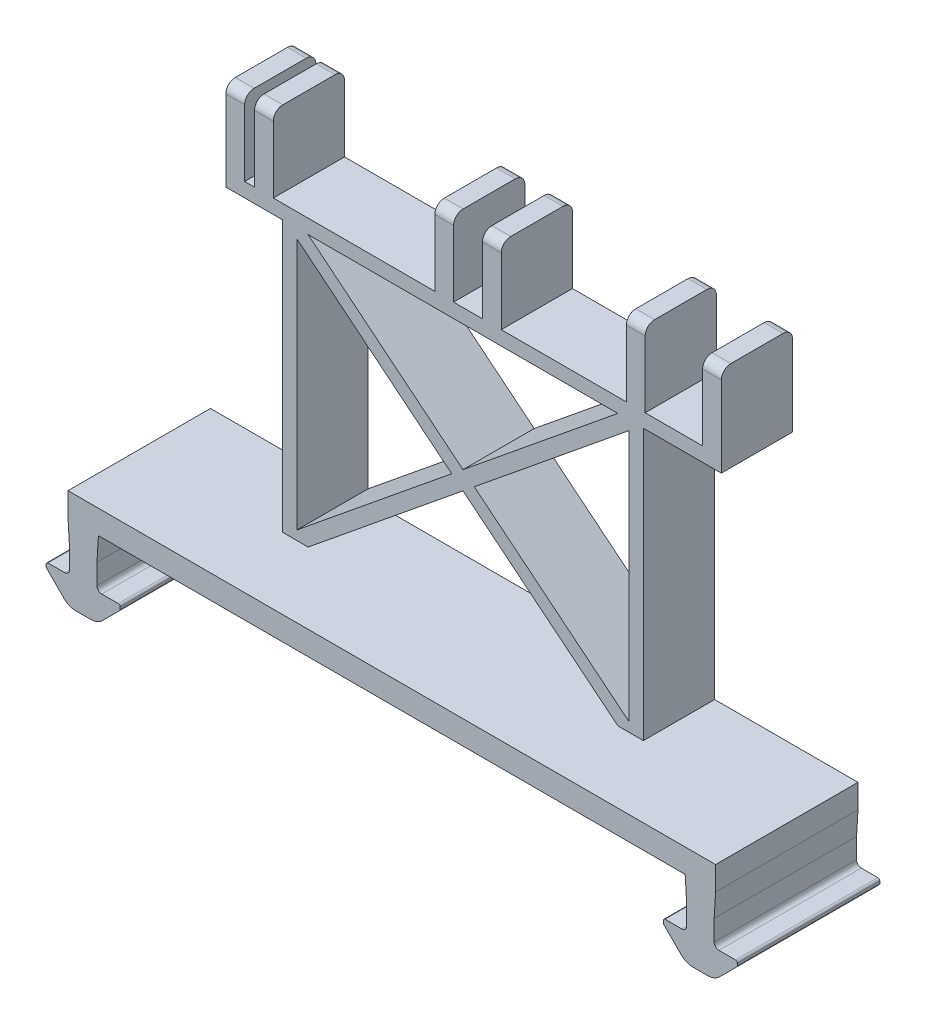
SolidWorks part; units mm, degrees
ref_plane "Front Plane" through (0, 0, 0) normal (0, 0, 1) x (1, 0, 0)
ref_plane "Top Plane" through (0, 0, 0) normal (0, 1, 0) x (1, 0, 0)
ref_plane "Right Plane" through (0, 0, 0) normal (1, 0, 0) x (0, 0, -1)
sketch "Sketch1" plane through (0, 0, 0) normal (0, 0, 1) x (1, 0, 0)
  line L7 (0, 0) -> (0, 26.663) construction
  line L8 (-2.0169, 6.858) -> (2.0169, 6.858)
  line L9 (5.3755, 8.2492) -> (10.0266, 12.9003)
  line L10 (10.287, 13.5289) -> (10.287, 14.0979)
  line L11 (9.398, 14.9869) -> (4.953, 14.9869)
  line L12 (4.064, 15.8759) -> (4.064, 27.6869)
  line L13 (0, 0) -> (20.2214, 20.2214) construction
  line L14 (-4.064, 15.8759) -> (-4.064, 27.6869)
  line L15 (-9.398, 14.9869) -> (-4.953, 14.9869)
  line L16 (-10.287, 13.5289) -> (-10.287, 14.0979)
  line L17 (-5.3755, 8.2492) -> (-10.0266, 12.9003)
  line L19 (163.0831, 6.858) -> (167.1169, 6.858)
  line L20 (170.4755, 8.2492) -> (175.1266, 12.9003)
  line L21 (175.387, 13.5289) -> (175.387, 14.0979)
  line L22 (174.498, 14.9869) -> (170.053, 14.9869)
  line L23 (169.164, 15.8759) -> (169.164, 27.6869)
  line L24 (161.036, 15.8759) -> (161.036, 27.6869)
  line L25 (155.702, 14.9869) -> (160.147, 14.9869)
  line L26 (154.813, 13.5289) -> (154.813, 14.0979)
  line L27 (159.7245, 8.2492) -> (155.0734, 12.9003)
  line L29 (-4.064, 27.6869) -> (-4.064, 34.0369)
  line L30 (-4.064, 34.0369) -> (169.164, 34.0369)
  line L31 (169.164, 34.0369) -> (169.164, 27.6869)
  line L32 (4.064, 27.6869) -> (161.036, 27.6869)
  arc A0 (10.0266, 12.9003) -> (10.287, 13.5289) centre (9.398, 13.5289) ccw
  arc A1 (9.398, 14.9869) -> (10.287, 14.0979) centre (9.398, 14.0979) cw
  arc A2 (4.953, 14.9869) -> (4.064, 15.8759) centre (4.953, 15.8759) cw
  arc A3 (2.0169, 6.858) -> (5.3755, 8.2492) centre (2.0169, 11.6078) ccw
  arc A4 (-2.0169, 6.858) -> (-5.3755, 8.2492) centre (-2.0169, 11.6078) cw
  arc A5 (-4.953, 14.9869) -> (-4.064, 15.8759) centre (-4.953, 15.8759) ccw
  arc A6 (-9.398, 14.9869) -> (-10.287, 14.0979) centre (-9.398, 14.0979) ccw
  arc A7 (-10.0266, 12.9003) -> (-10.287, 13.5289) centre (-9.398, 13.5289) cw
  arc A8 (175.1266, 12.9003) -> (175.387, 13.5289) centre (174.498, 13.5289) ccw
  arc A9 (174.498, 14.9869) -> (175.387, 14.0979) centre (174.498, 14.0979) cw
  arc A10 (170.053, 14.9869) -> (169.164, 15.8759) centre (170.053, 15.8759) cw
  arc A11 (167.1169, 6.858) -> (170.4755, 8.2492) centre (167.1169, 11.6078) ccw
  arc A12 (163.0831, 6.858) -> (159.7245, 8.2492) centre (163.0831, 11.6078) cw
  arc A13 (160.147, 14.9869) -> (161.036, 15.8759) centre (160.147, 15.8759) ccw
  arc A14 (155.702, 14.9869) -> (154.813, 14.0979) centre (155.702, 14.0979) ccw
  arc A15 (155.0734, 12.9003) -> (154.813, 13.5289) centre (155.702, 13.5289) cw
  point P1 (-4.064, 14.9869)
  point P20 (4.064, 14.9869)
  point P34 (0, 6.858)
  point P36 (161.036, 14.9869)
  point P63 (165.1, 6.858)
  dimension "D6" = 0.889
  dimension "D9" = 4.7498
  dimension "D1" = 12.7
  dimension "D2" = 4.064
  dimension "D3" = 6.858
  dimension "D4" = 10.287
  dimension "D5" = 2.032
  dimension "D7" = 0.569
  dimension "D8" = 45
  dimension "D11" = 165.1
  dimension "D12" = 6.35
  dimension "D10" = 2
extrude "Boss-Extrude2" add sketch "Sketch1" along normal blind 38.1
sketch "Sketch7" plane through (0, 0, 0) normal (0, 0, 1) x (1, 0, 0)
  line L0 (82.55, 68.2701) -> (82.55, 42.7511) construction
  line L1 (130.81, 106.4269) -> (169.164, 106.4269)
  line L3 (169.164, 34.0369) -> (-4.064, 34.0369) construction
  line L4 (-4.064, 34.0369) -> (-4.064, 15.8759) construction
  line L6 (34.29, 106.4269) -> (34.29, 34.0369)
  line L7 (34.29, 34.0369) -> (38.1, 34.0369)
  line L8 (130.81, 106.4269) -> (130.81, 34.0369)
  line L9 (-4.064, 110.2369) -> (169.164, 110.2369)
  line L10 (-4.064, 110.2369) -> (-4.064, 106.4269)
  line L11 (-4.064, 106.4269) -> (34.29, 106.4269)
  line L12 (169.164, 110.2369) -> (169.164, 106.4269)
  line L13 (38.1, 34.0369) -> (38.1, 106.4269)
  line L14 (127, 106.4269) -> (127, 34.0369)
  line L15 (38.1, 106.4269) -> (127, 106.4269)
  line L16 (127, 34.0369) -> (130.81, 34.0369)
  point P4 (82.55, 34.0369)
  point P15 (82.55, 110.2369)
  dimension "D1" = 72.39
  dimension "D2" = 3.81
  dimension "D3" = 3.81
  dimension "D4" = 44.45
extrude "Boss-Extrude6" add sketch "Sketch7" along normal blind 19.05
sketch "Sketch6" plane through (0, 110.2369, 0) normal (0, 1, 0) x (1, 0, 0)
  line L1 (19.1008, 0) -> (24.1808, 0)
  line L2 (19.1008, 0) -> (19.1008, -19.05)
  line L3 (19.1008, -19.05) -> (24.1808, -19.05)
  line L4 (24.1808, 0) -> (24.1808, -19.05)
  line L24 (169.164, 0) -> (130.81, 0) construction
  line L25 (26.7208, 0) -> (26.7208, -19.05)
  line L26 (-4.064, -38.1) -> (-4.064, 0) construction
  line L27 (26.7208, -19.05) -> (31.8008, -19.05)
  line L28 (31.8008, 0) -> (31.8008, -19.05)
  line L29 (26.7208, 0) -> (31.8008, 0)
  line L30 (75.0062, 0) -> (75.0062, -19.05)
  line L31 (75.0062, -19.05) -> (80.0862, -19.05)
  line L32 (80.0862, 0) -> (80.0862, -19.05)
  line L33 (75.0062, 0) -> (80.0862, 0)
  line L34 (87.7062, 0) -> (87.7062, -19.05)
  line L35 (87.7062, -19.05) -> (92.7862, -19.05)
  line L36 (92.7862, 0) -> (92.7862, -19.05)
  line L37 (87.7062, 0) -> (92.7862, 0)
  line L38 (126.2634, 0) -> (126.2634, -19.05)
  line L39 (126.2634, -19.05) -> (131.3434, -19.05)
  line L40 (131.3434, 0) -> (131.3434, -19.05)
  line L41 (126.2634, 0) -> (131.3434, 0)
  line L42 (146.5834, 0) -> (146.5834, -19.05)
  line L43 (146.5834, -19.05) -> (151.6634, -19.05)
  line L44 (151.6634, 0) -> (151.6634, -19.05)
  line L45 (146.5834, 0) -> (151.6634, 0)
  line L46 (-4.064, -38.1) -> (-4.064, 0) construction
  dimension "D1" = 5.08
  dimension "D2" = 19.05
  dimension "D4" = 28.2448
  dimension "D5" = 5.08
  dimension "D6" = 5.08
  dimension "D3" = 5.08
  dimension "D7" = 5.08
  dimension "D8" = 5.08
  dimension "D9" = 30.7848
  dimension "D10" = 84.1502
  dimension "D11" = 91.7702
  dimension "D12" = 150.6474
  dimension "D13" = 135.4074
extrude "Boss-Extrude5" add sketch "Sketch6" along normal blind 20.32
sketch "Sketch10" plane through (0, 0, 0) normal (0, 0, 1) x (1, 0, 0)
  line L1 (19.1008, 110.2369) -> (-4.064, 110.2369)
  line L2 (19.1008, 110.2369) -> (19.1008, 106.4269)
  line L3 (19.1008, 106.4269) -> (-4.064, 106.4269)
  line L4 (-4.064, 110.2369) -> (-4.064, 106.4269)
  line L5 (151.6634, 110.2369) -> (169.164, 110.2369)
  line L6 (151.6634, 110.2369) -> (151.6634, 106.4269)
  line L7 (151.6634, 106.4269) -> (169.164, 106.4269)
  line L8 (169.164, 110.2369) -> (169.164, 106.4269)
extrude "Cut-Extrude3" cut sketch "Sketch10" along normal up to surface (19.05 mm away) up to face at (82.6968, 107.9085, 19.05)
fillet "Fillet1" radius 2.54 12 edges at (149.1234, 130.5569, 0) (128.8034, 130.5569, 0) (149.1234, 130.5569, 19.05) (128.8034, 130.5569, 19.05) (90.2462, 130.5569, 0) (90.2462, 130.5569, 19.05) (77.5462, 130.5569, 19.05) (77.5462, 130.5569, 0) (29.2608, 130.5569, 0) (21.6408, 130.5569, 0) (21.6408, 130.5569, 19.05) (29.2608, 130.5569, 19.05)
sketch "Sketch11" plane through (0, 0, 0) normal (0, 0, 1) x (1, 0, 0)
  line L0 (38.1, 103.9702) -> (79.533, 70.2319)
  line L1 (38.1, 34.0369) -> (38.1, 106.4269) construction
  line L2 (169.164, 34.0369) -> (-4.064, 34.0369) construction
  line L3 (123.983, 34.0369) -> (127, 34.0369)
  line L4 (127, 34.0369) -> (127, 36.4936)
  line L5 (127, 106.4269) -> (127, 34.0369) construction
  line L6 (127, 36.4936) -> (85.567, 70.2319)
  line L7 (38.1, 106.4269) -> (127, 106.4269) construction
  line L8 (41.117, 106.4269) -> (38.1, 106.4269)
  line L9 (38.1, 106.4269) -> (38.1, 103.9702)
  line L10 (123.983, 106.4269) -> (127, 106.4269)
  line L11 (127, 106.4269) -> (127, 103.9702)
  line L12 (127, 103.9702) -> (85.567, 70.2319)
  line L13 (41.117, 34.0369) -> (38.1, 34.0369)
  line L14 (38.1, 34.0369) -> (38.1, 36.4936)
  line L15 (38.1, 36.4936) -> (79.533, 70.2319)
  line L16 (38.1, 34.0369) -> (127, 106.4269) construction
  line L17 (38.1, 106.4269) -> (127, 34.0369) construction
  line L18 (82.55, 67.7752) -> (41.117, 34.0369)
  line L19 (82.55, 67.7752) -> (123.983, 34.0369)
  line L20 (82.55, 72.6886) -> (123.983, 106.4269)
  line L21 (82.55, 72.6886) -> (41.117, 106.4269)
  dimension "D1" = 3.81
  dimension "D2" = 3.81
extrude "Boss-Extrude7" add sketch "Sketch11" along normal up to surface (19.05 mm away) up to face at (82.7151, 106.665, 19.05)
sketch "Sketch3" plane through (0, 0, 38.1) normal (0, 0, 1) x (1, 0, 0)
  line L27 (-3.937, 21.3369) -> (3.937, 21.3369) construction
  line L28 (4.064, 27.6869) -> (3.683, 21.3369)
  line L29 (-4.064, 27.6869) -> (-3.683, 21.3369)
  line L40 (-4.064, 34.0369) -> (-4.064, 15.8759) construction
  line L41 (-1004.064, 27.6869) -> (4.064, 27.6869) construction
  line L42 (161.036, 27.6869) -> (161.417, 21.3369)
  line L43 (169.164, 27.6869) -> (168.783, 21.3369)
  line L44 (169.164, 15.8759) -> (169.164, 34.0369) construction
  line L57 (5.1061, 8.5186) -> (9.7572, 13.1697)
  line L58 (9.906, 13.5289) -> (9.906, 14.0979)
  line L59 (9.398, 14.6059) -> (4.953, 14.6059)
  line L61 (3.683, 15.8759) -> (3.683, 28.0679)
  line L62 (3.683, 28.0679) -> (161.417, 28.0679)
  line L66 (161.417, 28.0679) -> (161.417, 15.8759)
  line L67 (160.147, 14.6059) -> (155.702, 14.6059)
  line L68 (155.194, 14.0979) -> (155.194, 13.5289)
  line L69 (155.3428, 13.1697) -> (159.9939, 8.5186)
  line L80 (163.0831, 7.239) -> (167.1169, 7.239)
  line L81 (170.2061, 8.5186) -> (174.8572, 13.1697)
  line L82 (175.006, 13.5289) -> (175.006, 14.0979)
  line L85 (174.498, 14.6059) -> (170.053, 14.6059)
  line L86 (168.783, 15.8759) -> (168.783, 33.6559)
  line L91 (168.783, 33.6559) -> (-3.683, 33.6559)
  line L93 (-3.683, 33.6559) -> (-3.683, 15.8759)
  line L95 (-4.953, 14.6059) -> (-9.398, 14.6059)
  line L97 (-9.906, 14.0979) -> (-9.906, 13.5289)
  line L99 (-9.7572, 13.1697) -> (-5.1061, 8.5186)
  line L101 (-2.0169, 7.239) -> (2.0169, 7.239)
  line L103 (5.1061, 8.5186) -> (9.7572, 13.1697)
  line L105 (9.906, 13.5289) -> (9.906, 14.0979)
  line L109 (9.398, 14.6059) -> (4.953, 14.6059)
  line L110 (3.683, 15.8759) -> (3.683, 21.3369)
  line L112 (161.417, 21.3369) -> (161.417, 15.8759)
  line L113 (160.147, 14.6059) -> (155.702, 14.6059)
  line L114 (155.194, 14.0979) -> (155.194, 13.5289)
  line L115 (155.3428, 13.1697) -> (159.9939, 8.5186)
  line L116 (163.0831, 7.239) -> (167.1169, 7.239)
  line L117 (170.2061, 8.5186) -> (174.8572, 13.1697)
  line L118 (175.006, 13.5289) -> (175.006, 14.0979)
  line L119 (174.498, 14.6059) -> (170.053, 14.6059)
  line L120 (168.783, 15.8759) -> (168.783, 21.3369)
  line L122 (-3.683, 21.3369) -> (-3.683, 15.8759)
  line L123 (-4.953, 14.6059) -> (-9.398, 14.6059)
  line L124 (-9.906, 14.0979) -> (-9.906, 13.5289)
  line L125 (-9.7572, 13.1697) -> (-5.1061, 8.5186)
  line L126 (-2.0169, 7.239) -> (2.0169, 7.239)
  line L137 (161.036, 27.6869) -> (1318.008, 27.6869) construction
  line L138 (19.1008, 130.5569) -> (24.1808, 130.5569) construction
  line L139 (24.13, 130.5569) -> (26.7716, 130.5569)
  line L140 (24.13, 130.5569) -> (24.13, 110.2369)
  line L141 (24.13, 110.2369) -> (26.7716, 110.2369)
  line L142 (26.7716, 130.5569) -> (26.7716, 110.2369)
  line L143 (126.2634, 130.5569) -> (131.3434, 130.5569) construction
  line L144 (80.0354, 130.5569) -> (87.757, 130.5569)
  line L145 (80.0354, 130.5569) -> (80.0354, 110.2369)
  line L146 (80.0354, 110.2369) -> (87.757, 110.2369)
  line L147 (87.757, 130.5569) -> (87.757, 110.2369)
  line L148 (131.2926, 130.5569) -> (146.6342, 130.5569)
  line L149 (131.2926, 130.5569) -> (131.2926, 110.2369)
  line L150 (131.2926, 110.2369) -> (146.6342, 110.2369)
  line L151 (146.6342, 130.5569) -> (146.6342, 110.2369)
  line L152 (126.2634, 110.2369) -> (92.7862, 110.2369) construction
  line L153 (24.1808, 128.0169) -> (24.1808, 110.2369) construction
  line L154 (26.7208, 128.0169) -> (26.7208, 110.2369) construction
  line L155 (80.0862, 128.0169) -> (80.0862, 110.2369) construction
  line L156 (87.7062, 128.0169) -> (87.7062, 110.2369) construction
  line L157 (5.3755, 8.2492) -> (10.0266, 12.9003)
  line L158 (10.287, 13.5289) -> (10.287, 14.0979)
  line L159 (9.398, 14.9869) -> (4.953, 14.9869)
  line L160 (4.064, 15.8759) -> (4.064, 27.6869)
  line L161 (4.064, 27.6869) -> (161.036, 27.6869)
  line L162 (161.036, 27.6869) -> (161.036, 15.8759)
  line L163 (160.147, 14.9869) -> (155.702, 14.9869)
  line L164 (154.813, 14.0979) -> (154.813, 13.5289)
  line L165 (155.0734, 12.9003) -> (159.7245, 8.2492)
  line L166 (163.0831, 6.858) -> (167.1169, 6.858)
  line L167 (170.4755, 8.2492) -> (175.1266, 12.9003)
  line L168 (175.387, 13.5289) -> (175.387, 14.0979)
  line L169 (174.498, 14.9869) -> (170.053, 14.9869)
  line L170 (169.164, 15.8759) -> (169.164, 34.0369)
  line L171 (169.164, 34.0369) -> (-4.064, 34.0369)
  line L172 (-4.064, 34.0369) -> (-4.064, 15.8759)
  line L173 (-4.953, 14.9869) -> (-9.398, 14.9869)
  line L174 (-10.287, 14.0979) -> (-10.287, 13.5289)
  line L175 (-10.0266, 12.9003) -> (-5.3755, 8.2492)
  line L176 (-2.0169, 6.858) -> (2.0169, 6.858)
  line L177 (5.3755, 8.2492) -> (10.0266, 12.9003)
  line L178 (10.287, 13.5289) -> (10.287, 14.0979)
  line L179 (9.398, 14.9869) -> (4.953, 14.9869)
  line L180 (4.064, 15.8759) -> (4.064, 27.6869)
  line L182 (161.036, 27.6869) -> (161.036, 15.8759)
  line L183 (160.147, 14.9869) -> (155.702, 14.9869)
  line L184 (154.813, 14.0979) -> (154.813, 13.5289)
  line L185 (155.0734, 12.9003) -> (159.7245, 8.2492)
  line L186 (163.0831, 6.858) -> (167.1169, 6.858)
  line L187 (170.4755, 8.2492) -> (175.1266, 12.9003)
  line L188 (175.387, 13.5289) -> (175.387, 14.0979)
  line L189 (174.498, 14.9869) -> (170.053, 14.9869)
  line L190 (169.164, 15.8759) -> (169.164, 27.6869)
  line L192 (-4.064, 27.6869) -> (-4.064, 15.8759)
  line L193 (-4.953, 14.9869) -> (-9.398, 14.9869)
  line L194 (-10.287, 14.0979) -> (-10.287, 13.5289)
  line L195 (-10.0266, 12.9003) -> (-5.3755, 8.2492)
  line L196 (-2.0169, 6.858) -> (2.0169, 6.858)
  line L197 (87.7062, 130.5569) -> (92.7862, 130.5569) construction
  line L198 (131.3434, 128.0169) -> (131.3434, 110.2369) construction
  line L199 (146.5834, 128.0169) -> (146.5834, 110.2369) construction
  arc A96 (2.0169, 7.239) -> (5.1061, 8.5186) centre (2.0169, 11.6078) ccw
  arc A97 (9.7572, 13.1697) -> (9.906, 13.5289) centre (9.398, 13.5289) ccw
  arc A98 (9.906, 14.0979) -> (9.398, 14.6059) centre (9.398, 14.0979) ccw
  arc A99 (3.683, 15.8759) -> (4.953, 14.6059) centre (4.953, 15.8759) ccw
  arc A100 (160.147, 14.6059) -> (161.417, 15.8759) centre (160.147, 15.8759) ccw
  arc A101 (155.702, 14.6059) -> (155.194, 14.0979) centre (155.702, 14.0979) ccw
  arc A102 (155.194, 13.5289) -> (155.3428, 13.1697) centre (155.702, 13.5289) ccw
  arc A103 (159.9939, 8.5186) -> (163.0831, 7.239) centre (163.0831, 11.6078) ccw
  arc A104 (167.1169, 7.239) -> (170.2061, 8.5186) centre (167.1169, 11.6078) ccw
  arc A105 (174.8572, 13.1697) -> (175.006, 13.5289) centre (174.498, 13.5289) ccw
  arc A106 (175.006, 14.0979) -> (174.498, 14.6059) centre (174.498, 14.0979) ccw
  arc A107 (168.783, 15.8759) -> (170.053, 14.6059) centre (170.053, 15.8759) ccw
  arc A108 (-4.953, 14.6059) -> (-3.683, 15.8759) centre (-4.953, 15.8759) ccw
  arc A109 (-9.398, 14.6059) -> (-9.906, 14.0979) centre (-9.398, 14.0979) ccw
  arc A110 (-9.906, 13.5289) -> (-9.7572, 13.1697) centre (-9.398, 13.5289) ccw
  arc A111 (-5.1061, 8.5186) -> (-2.0169, 7.239) centre (-2.0169, 11.6078) ccw
  arc A112 (2.0169, 7.239) -> (5.1061, 8.5186) centre (2.0169, 11.6078) ccw
  arc A113 (9.7572, 13.1697) -> (9.906, 13.5289) centre (9.398, 13.5289) ccw
  arc A114 (9.906, 14.0979) -> (9.398, 14.6059) centre (9.398, 14.0979) ccw
  arc A115 (3.683, 15.8759) -> (4.953, 14.6059) centre (4.953, 15.8759) ccw
  arc A116 (160.147, 14.6059) -> (161.417, 15.8759) centre (160.147, 15.8759) ccw
  arc A117 (155.702, 14.6059) -> (155.194, 14.0979) centre (155.702, 14.0979) ccw
  arc A118 (155.194, 13.5289) -> (155.3428, 13.1697) centre (155.702, 13.5289) ccw
  arc A119 (159.9939, 8.5186) -> (163.0831, 7.239) centre (163.0831, 11.6078) ccw
  arc A120 (167.1169, 7.239) -> (170.2061, 8.5186) centre (167.1169, 11.6078) ccw
  arc A121 (174.8572, 13.1697) -> (175.006, 13.5289) centre (174.498, 13.5289) ccw
  arc A122 (175.006, 14.0979) -> (174.498, 14.6059) centre (174.498, 14.0979) ccw
  arc A123 (168.783, 15.8759) -> (170.053, 14.6059) centre (170.053, 15.8759) ccw
  arc A124 (-4.953, 14.6059) -> (-3.683, 15.8759) centre (-4.953, 15.8759) ccw
  arc A125 (-9.398, 14.6059) -> (-9.906, 14.0979) centre (-9.398, 14.0979) ccw
  arc A126 (-9.906, 13.5289) -> (-9.7572, 13.1697) centre (-9.398, 13.5289) ccw
  arc A127 (-5.1061, 8.5186) -> (-2.0169, 7.239) centre (-2.0169, 11.6078) ccw
  arc A144 (2.0169, 6.858) -> (5.3755, 8.2492) centre (2.0169, 11.6078) ccw
  arc A145 (10.0266, 12.9003) -> (10.287, 13.5289) centre (9.398, 13.5289) ccw
  arc A146 (10.287, 14.0979) -> (9.398, 14.9869) centre (9.398, 14.0979) ccw
  arc A147 (4.064, 15.8759) -> (4.953, 14.9869) centre (4.953, 15.8759) ccw
  arc A148 (160.147, 14.9869) -> (161.036, 15.8759) centre (160.147, 15.8759) ccw
  arc A149 (155.702, 14.9869) -> (154.813, 14.0979) centre (155.702, 14.0979) ccw
  arc A150 (154.813, 13.5289) -> (155.0734, 12.9003) centre (155.702, 13.5289) ccw
  arc A151 (159.7245, 8.2492) -> (163.0831, 6.858) centre (163.0831, 11.6078) ccw
  arc A152 (167.1169, 6.858) -> (170.4755, 8.2492) centre (167.1169, 11.6078) ccw
  arc A153 (175.1266, 12.9003) -> (175.387, 13.5289) centre (174.498, 13.5289) ccw
  arc A154 (175.387, 14.0979) -> (174.498, 14.9869) centre (174.498, 14.0979) ccw
  arc A155 (169.164, 15.8759) -> (170.053, 14.9869) centre (170.053, 15.8759) ccw
  arc A156 (-4.953, 14.9869) -> (-4.064, 15.8759) centre (-4.953, 15.8759) ccw
  arc A157 (-9.398, 14.9869) -> (-10.287, 14.0979) centre (-9.398, 14.0979) ccw
  arc A158 (-10.287, 13.5289) -> (-10.0266, 12.9003) centre (-9.398, 13.5289) ccw
  arc A159 (-5.3755, 8.2492) -> (-2.0169, 6.858) centre (-2.0169, 11.6078) ccw
  arc A160 (2.0169, 6.858) -> (5.3755, 8.2492) centre (2.0169, 11.6078) ccw
  arc A161 (10.0266, 12.9003) -> (10.287, 13.5289) centre (9.398, 13.5289) ccw
  arc A162 (10.287, 14.0979) -> (9.398, 14.9869) centre (9.398, 14.0979) ccw
  arc A163 (4.064, 15.8759) -> (4.953, 14.9869) centre (4.953, 15.8759) ccw
  arc A164 (160.147, 14.9869) -> (161.036, 15.8759) centre (160.147, 15.8759) ccw
  arc A165 (155.702, 14.9869) -> (154.813, 14.0979) centre (155.702, 14.0979) ccw
  arc A166 (154.813, 13.5289) -> (155.0734, 12.9003) centre (155.702, 13.5289) ccw
  arc A167 (159.7245, 8.2492) -> (163.0831, 6.858) centre (163.0831, 11.6078) ccw
  arc A168 (167.1169, 6.858) -> (170.4755, 8.2492) centre (167.1169, 11.6078) ccw
  arc A169 (175.1266, 12.9003) -> (175.387, 13.5289) centre (174.498, 13.5289) ccw
  arc A170 (175.387, 14.0979) -> (174.498, 14.9869) centre (174.498, 14.0979) ccw
  arc A171 (169.164, 15.8759) -> (170.053, 14.9869) centre (170.053, 15.8759) ccw
  arc A172 (-4.953, 14.9869) -> (-4.064, 15.8759) centre (-4.953, 15.8759) ccw
  arc A173 (-9.398, 14.9869) -> (-10.287, 14.0979) centre (-9.398, 14.0979) ccw
  arc A174 (-10.287, 13.5289) -> (-10.0266, 12.9003) centre (-9.398, 13.5289) ccw
  arc A175 (-5.3755, 8.2492) -> (-2.0169, 6.858) centre (-2.0169, 11.6078) ccw
  dimension "D3" = 0
  dimension "D2" = 6.35
  dimension "D4" = 0.0508
  dimension "D5" = 0.0508
  dimension "D6" = 0.0508
  dimension "D7" = 0.0508
  dimension "D8" = 0.0508
  dimension "D9" = 0.0508
  dimension "D1" = 0.381
extrude "Clearance Trim" cut sketch "Sketch3" against normal up to surface (38.1 mm away) up to face at (82.55, 45.283, 0)
